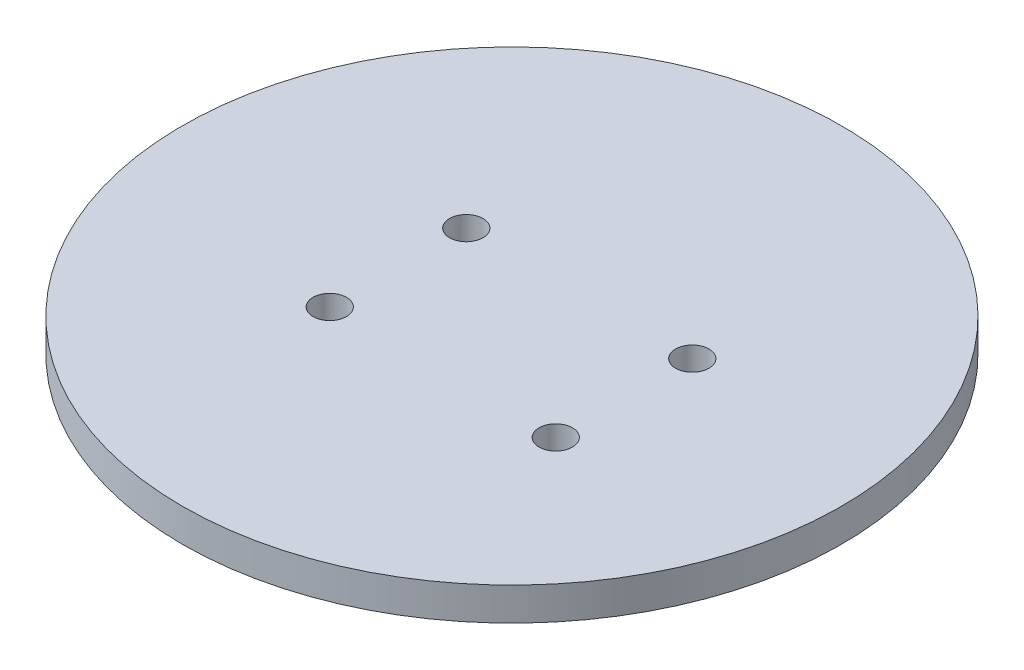
SolidWorks part; units mm, degrees
ref_plane "Front Plane" through (0, 0, 0) normal (0, 0, 1) x (1, 0, 0)
ref_plane "Top Plane" through (0, 0, 0) normal (0, 1, 0) x (1, 0, 0)
ref_plane "Right Plane" through (0, 0, 0) normal (1, 0, 0) x (0, 0, -1)
sketch "Sketch2" plane through (0, 0, 0) normal (0, 1, 0) x (1, 0, 0)
  circle A0 centre (0, 0) radius 35
  dimension "D1" = 70
extrude "Boss-Extrude1" add sketch "Sketch2" along normal blind 3.5
ref_plane "Plane1" through (-4, 0, 0) normal (1, 0, 0) x (0, 0, -1)
sketch "Sketch33" plane through (0, 0, 0) normal (0, -1, 0) x (1, 0, 0)
  circle A0 centre (0, 0) radius 29
  dimension "D1" = 58
extrude "Boss-Extrude3" add sketch "Sketch33" along normal blind 2.2
ref_plane "Plane2" through (0, -4.2, 0) normal (0, -1, 0) x (-1, 0, 0)
sketch "Sketch35" plane through (64.9204, -4.2, -6.6124) normal (0, 1, 0) x (1, 0, 0)
  line L0 (-64.9204, 22.3876) -> (-64.9204, -51.1324) construction
  line L1 (-64.9204, -6.5857) -> (-104.2271, -6.5857) construction
  line L3 (-62.0204, -8.2857) -> (-67.8204, -8.2857)
  line L4 (-62.0204, -8.2857) -> (-62.0204, -4.8857)
  line L5 (-62.0204, -4.8857) -> (-67.8204, -4.8857)
  line L6 (-67.8204, -8.2857) -> (-67.8204, -4.8857)
  circle A0 centre (-64.9204, -6.6124) radius 29 construction
  circle A1 centre (-64.9204, -6.6124) radius 29 construction
  dimension "D1" = 3.4
  dimension "D2" = 5.8
  dimension "D3" = 1.7
  dimension "D4" = 2.9
extrude "Boss-Extrude4" add sketch "Sketch35" against normal blind 6
shell "Shell2" thickness 1 removed face at (0, -10.2, -0.0268) outward yes
sketch "Sketch39" plane through (0, -2.2, 0) normal (0, -1, 0) x (-1, 0, 0)
  circle A0 centre (0, 0) radius 4.25
  circle A1 centre (0, 0) radius 5.5
extrude "Boss-Extrude5" add sketch "Sketch39" along normal blind 9
sketch "Sketch41" plane through (0, -10.2, 0) normal (0, -1, 0) x (-1, 0, 0)
  line L0 (0, 1.7268) -> (0, -7.344) construction
  line L1 (-2.9, 1.7268) -> (2.9, 1.7268) construction
  circle A0 centre (0, 0) radius 3.7
  circle A1 centre (0, 0) radius 4.5
extrude "Boss-Extrude6" add sketch "Sketch41" along normal blind 4
sketch "Sketch42" plane through (0, 3.5, 0) normal (0, 1, 0) x (1, 0, 0)
  circle A0 centre (-10.5052, 5.6583) radius 1.775
  circle A1 centre (13.4948, 5.6583) radius 1.775
  circle A2 centre (13.4948, -8.8417) radius 1.775
  circle A3 centre (-10.5052, -8.8417) radius 1.775
  dimension "D1" = 2
  dimension "D2" = 2
extrude "Cut-Extrude1" cut sketch "Sketch42" against normal up to surface (5.7 mm away) up to face at (0, -2.2, -29)
